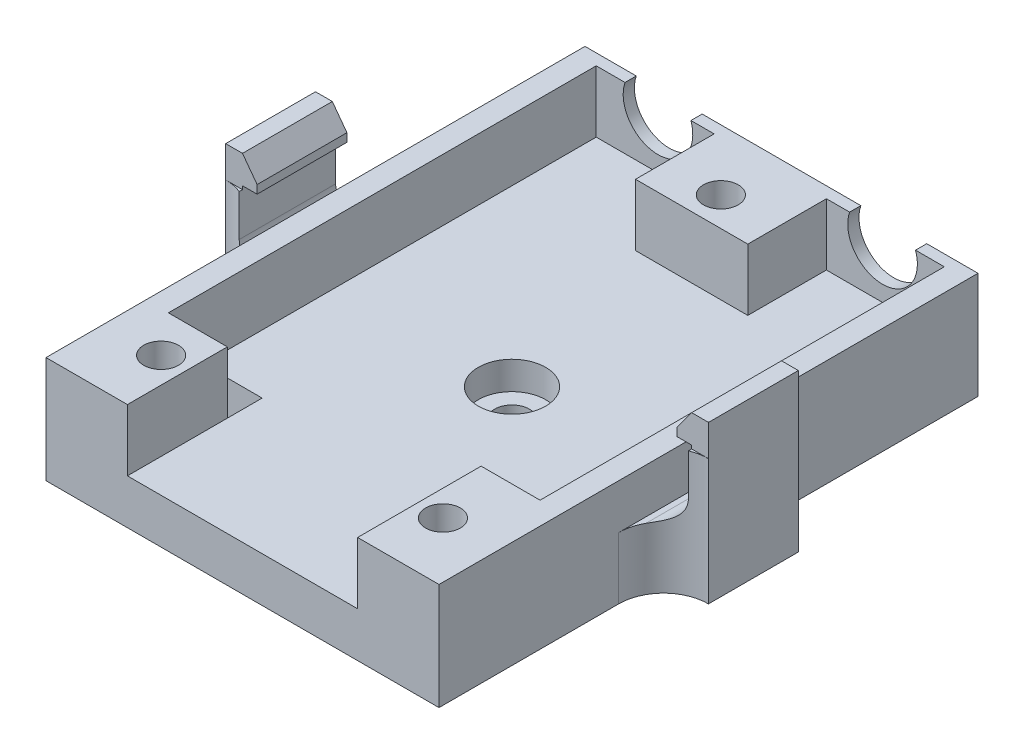
SolidWorks part; units mm, degrees
ref_plane "Front Plane" through (0, 0, 0) normal (0, 0, 1) x (1, 0, 0)
ref_plane "Top Plane" through (0, 0, 0) normal (0, 1, 0) x (1, 0, 0)
ref_plane "Right Plane" through (0, 0, 0) normal (1, 0, 0) x (0, 0, -1)
sketch "Sketch1" plane through (0, 0, 0) normal (0, 1, 0) x (1, 0, 0)
  line L1 (-17.5, 24) -> (17.5, 24)
  line L2 (-17.5, 24) -> (-17.5, -24)
  line L3 (-17.5, -24) -> (17.5, -24)
  line L4 (17.5, 24) -> (17.5, -24)
  line L5 (-44.2539, 0) -> (44.2539, 0) construction
  line L6 (0, -44.7868) -> (0, 44.7868) construction
  dimension "D2" = 35
  dimension "D1" = 48
  dimension "D3" = 24
  dimension "D4" = 17.5
extrude "Boss-Extrude1" add sketch "Sketch1" along normal blind 4
sketch "Sketch2" plane through (0, 4, 0) normal (0, 1, 0) x (1, 0, 0)
  line L1 (-15.5, 23) -> (15.5, 23)
  line L2 (-15.5, 23) -> (-15.5, -21)
  line L3 (-15.5, -21) -> (15.5, -21)
  line L4 (15.5, 23) -> (15.5, -21)
  line L6 (17.5, -24) -> (17.5, 24) construction
  line L7 (-17.5, -24) -> (17.5, -24) construction
  line M5 (-17.5, 24) -> (-17.5, -24)
  line M6 (-17.5, -24) -> (17.5, -24)
  line M7 (17.5, -24) -> (17.5, 24)
  line M8 (17.5, 24) -> (-17.5, 24)
  dimension "D1" = 2
  dimension "D2" = 3
  dimension "D3" = 31
  dimension "D4" = 44
extrude "Boss-Extrude2" add sketch "Sketch2" along normal blind 5.5 contours L1 L4 L3 L2 M8 M5 M6 M7 region at (0, 4, -23.4059)
sketch "Sketch3" plane through (0, 4, 0) normal (0, 1, 0) x (1, 0, 0)
  line L0 (-15.5, 23) -> (15.5, 23) construction
  line L1 (-5, 23) -> (5, 23)
  line L2 (-5, 23) -> (-5, 16)
  line L3 (-5, 16) -> (5, 16)
  line L4 (5, 23) -> (5, 16)
  line L5 (15.5, 23) -> (15.5, -21) construction
  line L7 (-15.5, -21) -> (-10.25, -21)
  line L8 (-15.5, -21) -> (-15.5, -13)
  line L9 (-15.5, -13) -> (-10.25, -13)
  line L10 (-10.25, -21) -> (-10.25, -13)
  line L11 (15.5, -21) -> (10.25, -21)
  line L12 (15.5, -21) -> (15.5, -13)
  line L13 (15.5, -13) -> (10.25, -13)
  line L14 (10.25, -21) -> (10.25, -13)
  dimension "D1" = 10
  dimension "D2" = 7
  dimension "D3" = 10.5
  dimension "D4" = 5.25
  dimension "D5" = 5.25
  dimension "D6" = 8
  dimension "D7" = 8
extrude "Boss-Extrude3" add sketch "Sketch3" along normal blind 5.5
sketch "Sketch4" plane through (0, 0, 24) normal (0, 0, 1) x (1, 0, 0)
  line L0 (-17.5, 9.5) -> (17.5, 9.5) construction
  line L1 (-10.25, 9.5) -> (10.25, 9.5)
  line L2 (-10.25, 9.5) -> (-10.25, 4)
  line L3 (-10.25, 4) -> (10.25, 4)
  line L4 (10.25, 9.5) -> (10.25, 4)
  line L5 (-17.5, 9.5) -> (-17.5, 0) construction
  line L6 (17.5, 9.5) -> (17.5, 0) construction
  dimension "D1" = 7.25
  dimension "D2" = 7.25
  dimension "D3" = 5.5
extrude "Cut-Extrude1" cut sketch "Sketch4" against normal up to surface (11 mm away) up to face at (-12.875, 6.75, 13)
sketch "Sketch5" plane through (0, 0, 0) normal (0, -1, 0) x (1, 0, 0)
  line L0 (44.2539, 0) -> (-44.2539, 0) construction
  line L1 (-2.55, 8.6) -> (2.45, 8.6)
  line L2 (-2.55, 8.6) -> (-2.55, 3.6)
  line L3 (-2.55, 3.6) -> (2.45, 3.6)
  line L4 (2.45, 8.6) -> (2.45, 3.6)
  line L5 (-2.55, -3.6) -> (2.45, -3.6)
  line L6 (-2.55, -3.6) -> (-2.55, -8.6)
  line L7 (-2.55, -8.6) -> (2.45, -8.6)
  line L8 (2.45, -3.6) -> (2.45, -8.6)
  line L9 (17.5, 24) -> (17.5, -24) construction
  dimension "D1" = 5
  dimension "D2" = 7.2
  dimension "D3" = 3.6
  dimension "D4" = 15.05
  dimension "D5" = 15.05
sketch "Sketch6" plane through (0, 0, -24) normal (0, 0, -1) x (-1, 0, 0)
  line L0 (-17.5, 9.5) -> (17.5, 9.5) construction
  line L3 (-17.5, 9.5) -> (-17.5, 0) construction
  arc A0 (-7.0657, 9.5) -> (-12.9343, 9.5) centre (-10, 8.5) cw
  arc A1 (12.9343, 9.5) -> (7.0657, 9.5) centre (10, 8.5) cw
  line M3 (17.5, 9.5) -> (-17.5, 9.5)
  dimension "D1" = 20
  dimension "D3" = 3.1
  dimension "D4" = 3.1
  dimension "D2" = 7.5
  dimension "D5" = 1
  dimension "D6" = 1
extrude "Cut-Extrude2" cut sketch "Sketch6" against normal blind 2 contours A0 M3 | A1 M3 region at (-10, 7.705, -24) region at (10, 7.705, -24)
sketch "Sketch7" plane through (0, 9.5, 0) normal (0, 1, 0) x (1, 0, 0)
  line L1 (-15.5, -12) -> (-10.25, -12)
  line L2 (-15.5, -12) -> (-15.5, -15.1)
  line L3 (-15.5, -15.1) -> (-10.25, -15.1)
  line L4 (-10.25, -12) -> (-10.25, -15.1)
  line L5 (-10.25, -24) -> (-10.25, -13) construction
  line L6 (-17.5, -24) -> (-10.25, -24) construction
  point P8 (0, 0)
  dimension "D1" = 3.1
  dimension "D2" = 5.25
  dimension "D3" = 8.9
extrude "Cut-Extrude3" cut sketch "Sketch7" against normal up to surface (9.5 mm away) up to face at (0, 0, 0)
sketch "Sketch8" plane through (0, 0, 0) normal (0, 1, 0) x (1, 0, 0)
  line L0 (0, -44.7868) -> (0, 44.7868) construction
  line L2 (7.0657, 24) -> (-7.0657, 24) construction
  circle A0 centre (-12.55, -18.7) radius 1.55
  circle A1 centre (12.55, -18.7) radius 1.55
  circle A2 centre (0, 18.6) radius 1.55
  dimension "D1" = 3.1
  dimension "D7" = 3.1
  dimension "D8" = 3.1
  dimension "D2" = 37.3
  dimension "D3" = 25.1
  dimension "D4" = 37.3
  dimension "D5" = 12.55
  dimension "D6" = 5.4
extrude "Cut-Extrude4" cut sketch "Sketch8" along direction (0, 1, 0) on the side against the normal blind 5.5 from surface starting at face at (-14.0461, 9.5, -1.975)
sketch "Sketch9" plane through (0, 0, 0) normal (0, 1, 0) x (1, 0, 0)
  line L0 (-35.1135, -20.6) -> (29.9959, -20.6) construction
  line L1 (-7.0657, 23) -> (-5, 23) construction
  line L2 (-35.1135, 21.9) -> (32.5575, 21.9) construction
  point P4 (-6.0329, 23)
  dimension "D1" = 43.6
  dimension "D2" = 42.5
extrude "Cut-Extrude5" cut sketch "Sketch5" against normal blind 2
sketch "Sketch10" plane through (0, 0, 0) normal (0, -1, 0) x (1, 0, 0)
  circle A0 centre (0, 0) radius 1.55
  dimension "D1" = 3.1
extrude "Cut-Extrude6" cut sketch "Sketch10" against normal up to surface (4 mm away) up to face at (-0.7885, 4, -0.8385)
sketch "Sketch11" plane through (0, 4, 0) normal (0, 1, 0) x (1, 0, 0)
  circle A0 centre (0, 0) radius 3
  dimension "D1" = 6
extrude "Cut-Extrude7" cut sketch "Sketch11" against normal blind 2.5
sketch "Sketch13" plane through (0, 0, 0) normal (0, 0, 1) x (1, 0, 0)
  line L0 (17.5, 0) -> (21.5, 0)
  line L1 (-35.1135, 0) -> (32.5575, 0) construction
  line L2 (55, 0) -> (-55, 0) construction
  line L3 (21.5, 0) -> (21.5, 14)
  line L4 (21.5, 14) -> (20, 14)
  line L5 (20, 14) -> (18.7, 12.243)
  line L6 (18.7, 12.243) -> (18.7, 11.5)
  line L7 (18.7, 11.5) -> (20, 11.5)
  line L8 (20, 11.5) -> (20, 5.5)
  line L9 (20, 5.5) -> (17.5, 5.5)
  line L11 (17.5, 9.5) -> (17.5, 0) construction
  line L12 (10.25, 9.5) -> (17.5, 9.5) construction
  line L13 (17.5, 5.5) -> (17.5, 0)
  dimension "D1" = 2.5
  dimension "D2" = 4
  dimension "D3" = 2.5
  dimension "D4" = 1.5
  dimension "D5" = 1.3
  dimension "D6" = 14
  dimension "D7" = 4
extrude "Boss-Extrude5" add sketch "Sketch13" along normal mid plane 8
fillet "Fillet1" radius 4 2 edges at (17.5, 2.75, -4) (17.5, 2.75, 4)
fillet "Fillet2" radius 2 1 edges at (20, 5.5, 0)
mirror "Mirror4" about plane through (0, 0, 0) normal (1, 0, 0) of "Boss-Extrude5"
fillet "Fillet3" radius 4 2 edges at (-17.5, 2.75, 4) (-17.5, 2.75, -4)
fillet "Fillet4" radius 2 1 edges at (-20, 5.5, 0)
sketch "Sketch14" plane through (0, 14, 0) normal (0, 1, 0) x (1, 0, 0)
  line L1 (-21.5, 4) -> (21.5, 4)
  line L2 (-21.5, 4) -> (-21.5, -4)
  line L3 (-21.5, -4) -> (21.5, -4)
  line L4 (21.5, 4) -> (21.5, -4)
  line L5 (-22.5, 6) -> (22.5, 6)
  line L6 (-22.5, 6) -> (-22.5, -6)
  line L7 (-22.5, -6) -> (22.5, -6)
  line L8 (22.5, 6) -> (22.5, -6)
  line M9 (21.5, -4) -> (21.5, 4)
  arc M10 (21.5, 4) -> (20, 4.2919) centre (21.5, 8) cw
  line M11 (20, 4.2919) -> (20, -4.2919)
  arc M12 (20, -4.2919) -> (21.5, -4) centre (21.5, -8) cw
  dimension "D1" = 2
  dimension "D2" = 1
  dimension "D3" = 2
  dimension "D4" = 1
extrude "Cut-Extrude11" cut sketch "Sketch14" against normal blind 2.8 contours L3 M11 M12 | L1 M11 M10 | L8 L5 L6 L7 L3 L2 L1 M11 M10 M9 M12 region at (20.3722, 14, -4.087) region at (20.3722, 14, 4.087) region at (0, 14, -5.5343)
equation "\"fWidth\"=35"
equation "\"D2@Sketch1\"=\"fWidth\""
equation "\"fLength\"= 48"
equation "\"D1@Sketch1\"=\"fLength\""
equation "\"D3@Sketch1\"=\"fLength\"/2"
equation "\"D4@Sketch1\"=\"fWidth\"/2"
equation "\"wThickness\"= 2"
equation "\"D1@Sketch2\"=\"wThickness\""
equation "\"D3@Sketch2\"=\"fWidth\"- 2* \"wThickness\""
equation "\"D4@Sketch2\"=\"fLength\"- 2 *\"wThickness\""
equation "\"wHeight\"= 5.5"
equation "\"D1@Boss-Extrude2\"=\"wHeight\""
equation "\"D3@Sketch3\"=(\"fWidth\"- 2 *\"wThickness\" - 10)/2"
equation "\"D4@Sketch5\"=(\"fWidth\"- 4.9)/2"
equation "\"D5@Sketch5\"=(\"fWidth\"- 4.9)/2"
equation "\"D3@Sketch4\"=\"wHeight\""
